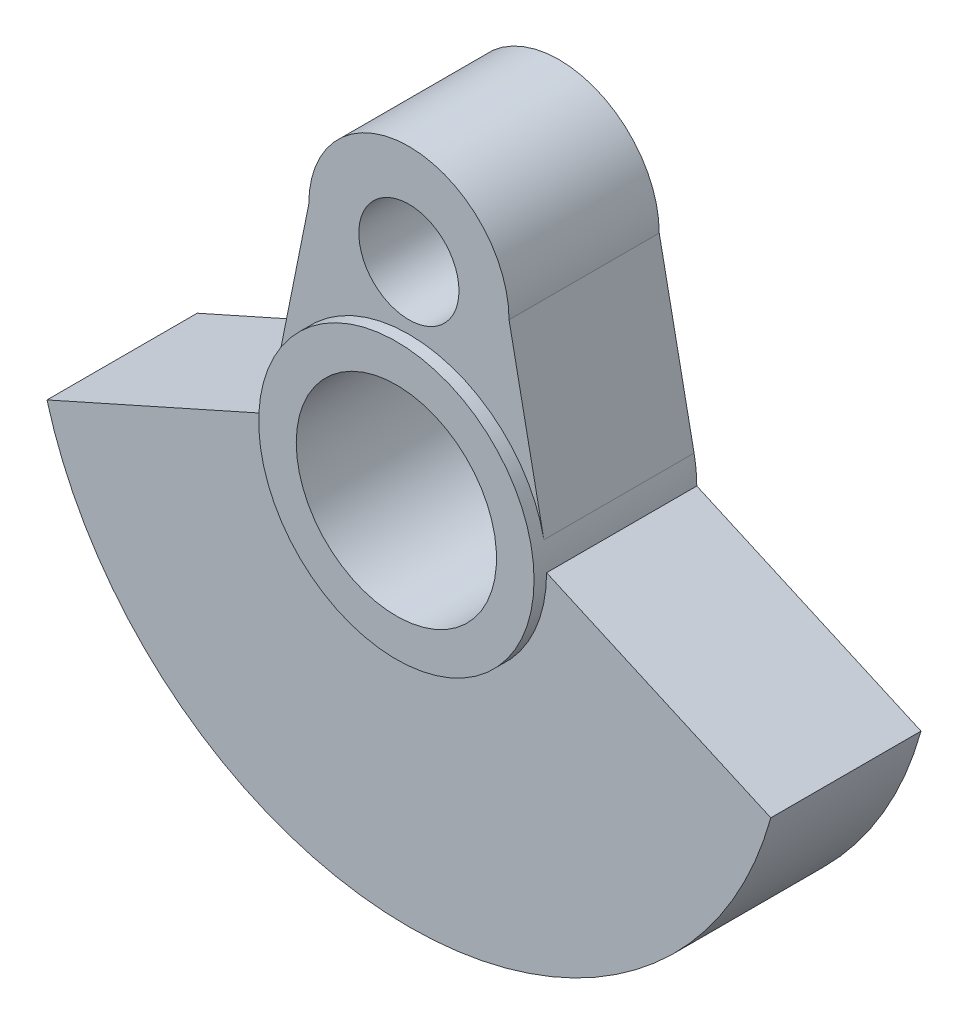
SolidWorks part; units mm, degrees
ref_plane "Front Plane" through (0, 0, 0) normal (0, 0, 1) x (1, 0, 0)
ref_plane "Top Plane" through (0, 0, 0) normal (0, 1, 0) x (1, 0, 0)
ref_plane "Right Plane" through (0, 0, 0) normal (1, 0, 0) x (0, 0, -1)
sketch "Sketch1" plane through (0, 0, 0) normal (0, 0, 1) x (1, 0, 0)
  line L0 (0, 0) -> (-11.1495, 0) construction
  line L1 (-11.1495, 0) -> (0, 0) construction
  line L2 (0, 0) -> (0, 8) construction
  line L3 (-14.4568, -4) -> (-5.5, 0)
  line L4 (14.4568, -4) -> (5.5, 0)
  line L5 (-4, 8) -> (-5.3919, 1.0853)
  line L6 (4, 8) -> (5.3919, 1.0853)
  circle A0 centre (0, 0) radius 5.5
  arc A1 (4, 8) -> (-4, 8) centre (0, 8) ccw
  circle A2 centre (0, 8) radius 2
  arc A3 (-14.4568, -4) -> (14.4568, -4) centre (0, 0) ccw
  circle A4 centre (0, 0) radius 4
  dimension "D1" = 11
  dimension "D2" = 8
  dimension "D3" = 4
  dimension "D4" = 15
  dimension "D7" = 8
  dimension "D5" = 4
  dimension "D6" = 8
extrude "Boss-Extrude1" add sketch "Sketch1" along normal mid plane 6 contours L3 A3 L4 A0 | L6 A1 L5 A0 A2 region at (0, -7.8111, 0) region at (-4.5455, 4.5124, 0)
extrude "Boss-Extrude2" add sketch "Sketch1<3>" along normal blind 6.5 from surface contours A0 A4 region at (-5.3181, 0.5299, 0) starting at face at (0, -6.125, -3)
sketch "Sketch1<3>" plane through (0, 0, 0) normal (0, 0, 1) x (1, 0, 0) same geometry as "Sketch1"
